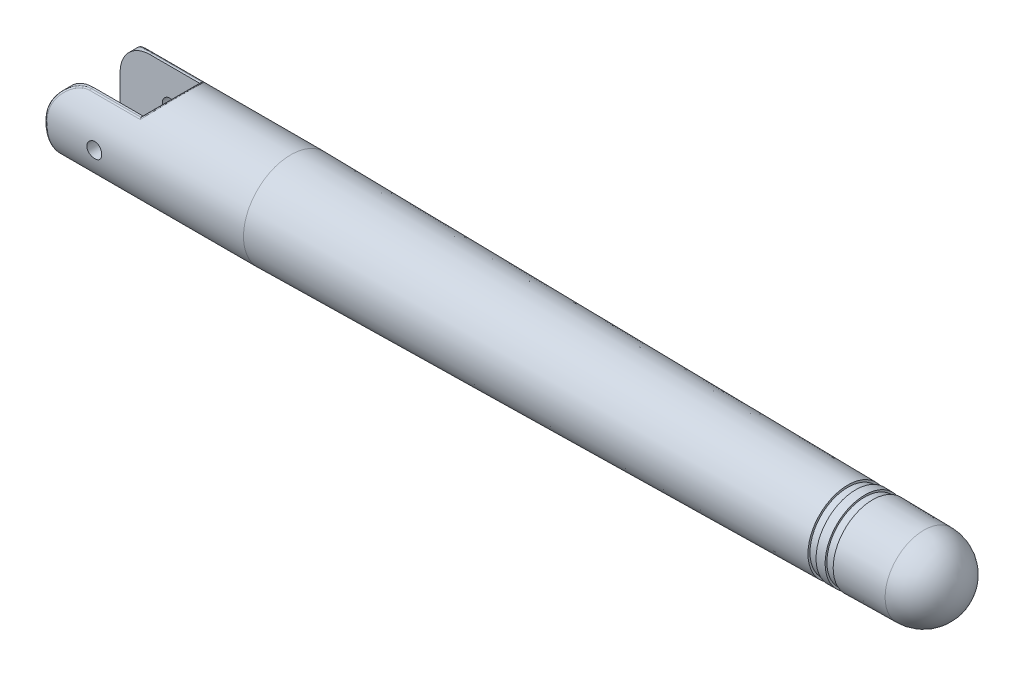
SolidWorks part; units mm, degrees
ref_plane "Спереди" through (0, 0, 0) normal (0, 0, 1) x (1, 0, 0)
ref_plane "Сверху" through (0, 0, 0) normal (0, 1, 0) x (1, 0, 0)
ref_plane "Справа" through (0, 0, 0) normal (1, 0, 0) x (0, 0, -1)
sketch "Эскиз1" plane through (0, 0, 0) normal (0, 0, 1) x (1, 0, 0)
  line L0 (0, 0) -> (87.5, 0) construction
  line L1 (0, 0) -> (0, 4.75)
  line L2 (0, 4.75) -> (20, 4.75)
  line L3 (20, 4.75) -> (76, 4.0019)
  line L4 (76, 4.0019) -> (76, 3.8)
  line L5 (76, 3.8) -> (76.8, 3.8)
  line L6 (76.8, 3.8) -> (76.8, 3.9912)
  line L7 (77.7, 3.9792) -> (77.7, 3.8)
  line L8 (77.7, 3.8) -> (78.5, 3.8)
  line L9 (78.5, 3.8) -> (78.5, 3.9685)
  line L10 (76.8, 3.9912) -> (77.7, 3.9792)
  line L11 (78.5, 3.9685) -> (83.6521, 3.8997)
  line L12 (0, 0) -> (87.5, 0)
  arc A0 (83.6521, 3.8997) -> (87.5, 0) centre (83.6, 0) cw
  dimension "D3" = 3.9
  dimension "D1" = 20
  dimension "D2" = 9.5
  dimension "D4" = 87.5
  dimension "D5" = 0.9
  dimension "D6" = 0.8
  dimension "D7" = 0.8
  dimension "D8" = 9
  dimension "D9" = 3.8
revolve "Повернуть1" add sketch "Эскиз1" angle 360 about L0
sketch "Эскиз2" plane through (0, 0, 0) normal (0, 1, 0) x (1, 0, 0)
  line L0 (0, 4.75) -> (0, -4.75) construction
  line L1 (0, -2.85) -> (8, -2.85)
  line L2 (0, -2.85) -> (0, 2.85)
  line L3 (0, 2.85) -> (8, 2.85)
  line L4 (8, -2.85) -> (8, 2.85)
  dimension "D1" = 5.7
  dimension "D2" = 8
extrude "Вырез-Вытянуть1" cut sketch "Эскиз2" along normal through all and the other way blind 3.5
sketch "Эскиз3" plane through (0, 0, 0) normal (0, 0, 1) x (1, 0, 0)
  line L0 (0, 0) -> (5, 0) construction
  line L1 (0, 3.8) -> (0, 3.55)
  line L2 (0, 3.8) -> (0, -4.75) construction
  line L4 (0, 3.55) -> (8, 3.55)
  line L5 (8, 3.55) -> (9.2, 4.75)
  line L6 (20, 4.75) -> (8, 4.75) construction
  line L7 (9.2, 4.75) -> (0, 4.75)
  line L8 (0, 4.75) -> (0, 3.8)
  circle A0 centre (5, 0) radius 0.75
  point P10 (7.9907, 3.638)
  dimension "D2" = 1.5
  dimension "D1" = 5
  dimension "D3" = 0.25
  dimension "D4" = 8
  dimension "D5" = 45
extrude "Вырез-Вытянуть2" cut sketch "Эскиз3" against normal through all both and the other way through all
fillet "Скругление2" radius 3 2 edges at (0, 3.55, -3.003) (0, 3.55, 3.003)
fillet "Скругление1" radius 0.25 6 edges at (0, -4.75, 0) (5.5, 3.55, -3.1559) (9.2, 4.75, 0) (5.5, 3.55, 3.1559) (0.5333, 2.2574, -4.1793) (1.4815, 3.1373, 3.5665)
